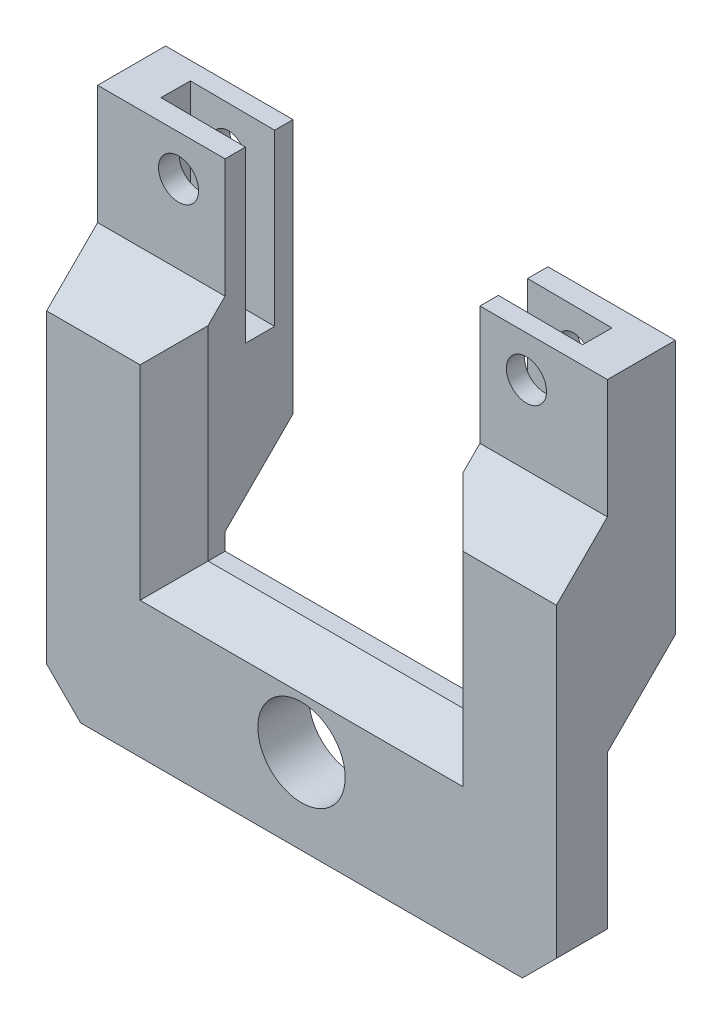
SolidWorks part; units mm, degrees
ref_plane "Front Plane" through (0, 0, 0) normal (0, 0, 1) x (1, 0, 0)
ref_plane "Top Plane" through (0, 0, 0) normal (0, 1, 0) x (1, 0, 0)
ref_plane "Right Plane" through (0, 0, 0) normal (1, 0, 0) x (0, 0, -1)
sketch "Sketch1" plane through (0, 0, 0) normal (0, 0, 1) x (1, 0, 0)
  line L1 (-19.05, 19.05) -> (19.05, 19.05)
  line L2 (-19.05, 19.05) -> (-19.05, -19.05)
  line L3 (-19.05, -19.05) -> (19.05, -19.05)
  line L4 (19.05, 19.05) -> (19.05, -19.05)
  line L5 (-19.05, 19.05) -> (19.05, -19.05) construction
  line L6 (-19.05, -19.05) -> (19.05, 19.05) construction
  point P0 (0, 0)
  dimension "D1" = 38.1
  dimension "D2" = 38.1
extrude "Boss-Extrude1" add sketch "Sketch1" against normal blind 8.89
sketch "Sketch3" plane through (0, 0, 0) normal (0, 0, 1) x (1, 0, 0)
  line L0 (19.05, -19.05) -> (19.05, 19.05) construction
  line L1 (-19.05, 19.05) -> (19.05, 19.05)
  line L2 (-19.05, 19.05) -> (-19.05, 6.35)
  line L3 (-19.05, 6.35) -> (19.05, 6.35)
  line L4 (19.05, 19.05) -> (19.05, 6.35)
  dimension "D1" = 12.7
extrude "Cut-Extrude1" cut sketch "Sketch3" against normal blind 3.81
sketch "Sketch4" plane through (0, 0, -3.81) normal (0, 0, 1) x (1, 0, 0)
  line L0 (0, 19.05) -> (0, 6.35) construction
  line L1 (19.05, 19.05) -> (-19.05, 19.05) construction
  line L2 (-19.05, 6.35) -> (19.05, 6.35) construction
  circle A0 centre (-13, 16.002) radius 1.27
  circle A1 centre (13, 16.002) radius 1.27
  dimension "D1" = 2.54
  dimension "D2" = 13
  dimension "D3" = 3.048
extrude "Cut-Extrude2" cut sketch "Sketch4" against normal through all
sketch "Sketch5" plane through (0, 0, -3.81) normal (0, 0, 1) x (1, 0, 0)
  line L1 (-9.4833, 0) -> (9.4833, 0)
  line L2 (-9.4833, 0) -> (-9.4833, 19.05)
  line L3 (-9.4833, 19.05) -> (9.4833, 19.05)
  line L4 (9.4833, 0) -> (9.4833, 19.05)
  line L5 (-9.4833, 0) -> (9.4833, 19.05) construction
  line L6 (-9.4833, 19.05) -> (9.4833, 0) construction
  line L7 (19.05, 19.05) -> (-19.05, 19.05) construction
  point P0 (0, 9.525)
  dimension "D1" = 18.9666
  dimension "D2" = 19.05
extrude "Cut-Extrude4" [suppressed] cut sketch "Sketch5" against normal through all
sketch "Sketch6" plane through (0, 0, 0) normal (0, 0, 1) x (1, 0, 0)
  line L0 (-9.525, -6.35) -> (9.525, -6.35)
  line L1 (-9.525, -6.35) -> (-9.525, 25.4)
  line L2 (-9.525, 25.4) -> (9.525, 25.4)
  line L3 (9.525, -6.35) -> (9.525, 25.4)
  line L4 (-9.525, -6.35) -> (9.525, 25.4) construction
  line L5 (-9.525, 25.4) -> (9.525, -6.35) construction
  line L7 (0, 19.05) -> (0, -19.05) construction
  line L8 (19.05, 19.05) -> (-19.05, 19.05) construction
  line L9 (-19.05, -19.05) -> (19.05, -19.05) construction
  point P0 (0, 9.525)
  dimension "D1" = 12.7
  dimension "D2" = 6.35
  dimension "D3" = 19.05
extrude "Cut-Extrude5" cut sketch "Sketch6" against normal through all
sketch "Sketch7" plane through (0, 19.05, 0) normal (0, 1, 0) x (1, 0, 0)
  line L0 (-19.05, 6.35) -> (19.05, 6.35) construction
  line L1 (-19.05, 8.89) -> (-19.05, 3.81) construction
  line L2 (19.05, 8.89) -> (19.05, 3.81) construction
  line L3 (0, 0) -> (0, 8.89) construction
  line L4 (-9.525, 8.89) -> (9.525, 8.89) construction
  line L5 (15.8827, 7.3231) -> (-15.8664, 7.5612)
  line L6 (15.8827, 7.3231) -> (15.8664, 5.1388)
  line L7 (-15.8664, 7.5612) -> (-15.8827, 5.3769)
  line L8 (15.8664, 5.1388) -> (-15.8827, 5.3769)
  line L9 (15.8827, 7.3231) -> (-15.8827, 5.3769) construction
  line L10 (-15.8664, 7.5612) -> (15.8664, 5.1388) construction
  point P12 (0, 6.35)
  dimension "D1" = 31.75
  dimension "D2" = 2.1844
extrude "Cut-Extrude6" cut sketch "Sketch7" against normal blind 12.7
sketch "Sketch8" plane through (0, 0, -8.89) normal (0, 0, -1) x (-1, 0, 0)
  line L0 (19.05, 19.05) -> (19.05, -19.05) construction
  line L1 (-19.05, -19.05) -> (19.05, -19.05)
  line L2 (-19.05, -19.05) -> (-19.05, 0)
  line L3 (-19.05, 0) -> (19.05, 0)
  line L4 (19.05, -19.05) -> (19.05, 0)
extrude "Cut-Extrude7" cut sketch "Sketch8" against normal blind 5.08
chamfer "Chamfer1" [suppressed] distance 0.381 angle 75
chamfer "Chamfer2" [suppressed] distance 0.635 distance2 3.81
chamfer "Chamfer3" [suppressed] distance 3.81 angle 45
chamfer "Chamfer4" [suppressed] distance 3.81 angle 45
sketch "Sketch9" plane through (0, 0, 0) normal (0, 0, 1) x (1, 0, 0)
  line L0 (-19.05, -12.7) -> (19.05, -12.7) construction
  line L1 (-19.05, 6.35) -> (-19.05, -19.05) construction
  line L2 (19.05, -19.05) -> (19.05, 6.35) construction
  line L5 (-19.05, -19.05) -> (19.05, -19.05) construction
  circle A0 centre (0, -12.7) radius 3.2639
  dimension "D2" = 6.5278
  dimension "D1" = 6.35
extrude "Cut-Extrude8" cut sketch "Sketch9" against normal through all
fillet "Fillet1" [suppressed] radius 2.54
fillet "Fillet2" [suppressed] radius 2.54
fillet "Fillet3" [suppressed] radius 10.16
fillet "Fillet5" [suppressed] radius 0.635
chamfer "Chamfer5" [suppressed] distance 1.27 angle 45
fillet "Fillet6" [suppressed] radius 12.7
sketch "Sketch10" plane through (0, 0, -3.81) normal (0, 0, 1) x (1, 0, 0)
  line L0 (0, -6.35) -> (0, 27.174) construction
  line L1 (-9.525, -6.35) -> (9.525, -6.35) construction
  circle A0 centre (-13, 16.002) radius 1.5
  circle A1 centre (13, 16.002) radius 1.5
  dimension "D1" = 3
extrude "Cut-Extrude9" cut sketch "Sketch10" against normal up to next
chamfer "Chamfer6" distance 5.08 angle 45 2 edges at (-14.2875, 0, -3.81) (14.2875, 0, -3.81)
chamfer "Chamfer7" distance 3.81 angle 45 2 edges at (-14.2875, 6.35, -3.81) (14.2875, 6.35, -3.81)
chamfer "Chamfer8" distance 2.54 angle 45 3 edges at (-9.525, 0, 0) (0, -6.35, 0) (9.525, 0, 0)
chamfer "Chamfer9" distance 2.54 angle 45 3 edges at (-19.05, -19.05, -1.905) (19.05, -19.05, -1.905) (0, -19.05, -3.81)
